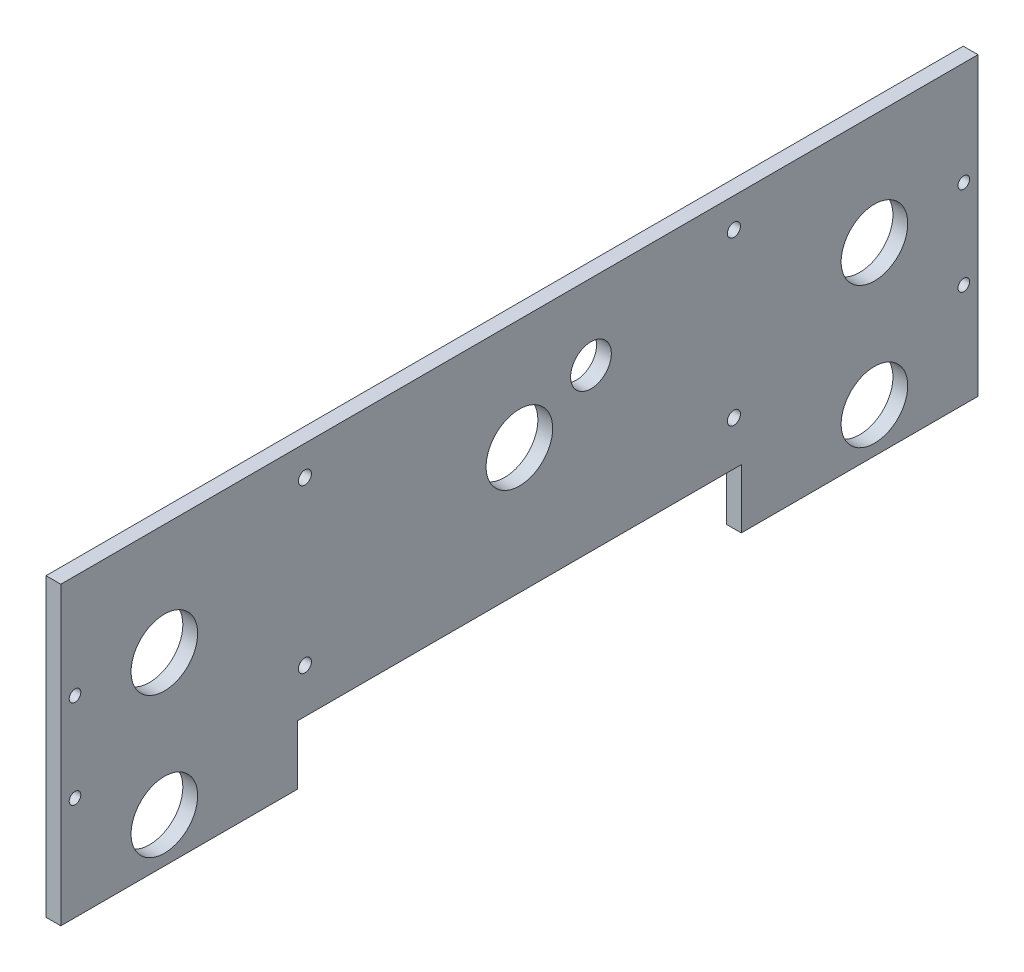
SolidWorks part; units mm, degrees
material "6061-T6 (SS)"
ref_plane "Front Plane" through (0, 0, 0) normal (0, 0, 1) x (1, 0, 0)
ref_plane "Top Plane" through (0, 0, 0) normal (0, 1, 0) x (1, 0, 0)
ref_plane "Right Plane" through (0, 0, 0) normal (1, 0, 0) x (0, 0, -1)
sketch "Sketch1" plane through (0, 0, 0) normal (1, 0, 0) x (0, 0, -1)
  line L1 (-196.85, 63.5) -> (196.85, 63.5)
  line L2 (-196.85, 63.5) -> (-196.85, -63.5)
  line L3 (-196.85, -63.5) -> (196.85, -63.5)
  line L4 (196.85, 63.5) -> (196.85, -63.5)
  line L5 (-196.85, 63.5) -> (196.85, -63.5) construction
  line L6 (-196.85, -63.5) -> (196.85, 63.5) construction
  point P0 (0, 0)
  dimension "D1" = 127
  dimension "D2" = 393.7
extrude "Boss-Extrude1" add sketch "Sketch1" along normal blind 6.35
sketch "Sketch2" plane through (6.35, 0, 0) normal (1, 0, 0) x (0, 0, -1)
  line L0 (-196.85, -63.5) -> (196.85, -63.5) construction
  line L1 (-152.4, 15.875) -> (0, 15.875) construction
  line L2 (-76.2, -34.925) -> (-76.2, 15.875) construction
  line L3 (0, 15.875) -> (152.4, 15.875) construction
  line L4 (76.2, -34.925) -> (76.2, 15.875) construction
  line L5 (196.85, 63.5) -> (-196.85, 63.5) construction
  line L6 (65.278, 53.34) -> (-56.642, 53.34) construction
  line L7 (65.278, 53.34) -> (65.278, -13.97) construction
  line L8 (65.278, -13.97) -> (-56.642, -13.97) construction
  line L9 (-56.642, 53.34) -> (-56.642, -13.97) construction
  line L10 (-196.85, -63.5) -> (196.85, -63.5) construction
  circle A0 centre (0, 15.875) radius 14.2875
  circle A1 centre (-152.4, 15.875) radius 14.2875
  circle A2 centre (152.4, 15.875) radius 14.2875
  circle A3 centre (-152.4, 15.875) radius 38.1 construction
  circle A4 centre (0, 15.875) radius 38.1 construction
  circle A5 centre (152.4, 15.875) radius 38.1 construction
  circle A6 centre (-76.2, -34.925) radius 6.35 construction
  circle A7 centre (76.2, -34.925) radius 6.35 construction
  circle A8 centre (-76.2, 9.525) radius 6.35 construction
  circle A9 centre (76.2, 9.525) radius 6.35 construction
  circle A11 centre (-152.4, -44.45) radius 14.2875
  circle A12 centre (152.4, -44.45) radius 14.2875
  circle A13 centre (0, 15.875) radius 29.21 construction
  circle A14 centre (30.7172, 31.115) radius 5.08 construction
  circle A15 centre (30.7172, 31.115) radius 8.75
  point P11 (0, 0)
  dimension "D1" = 28.575
  dimension "D5" = 76.2
  dimension "D7" = 12.7
  dimension "D14" = 28.575
  dimension "D15" = 19.05
  dimension "D17" = 28.575
  dimension "D20" = 58.42
  dimension "D21" = 10.16
  dimension "D22" = 17.5001
  dimension "D2" = 79.375
  dimension "D3" = 152.4
  dimension "D4" = 152.4
  dimension "D6" = 0
  dimension "D8" = 28.575
  dimension "D9" = 44.45
  dimension "D10" = 56.642
  dimension "D11" = 121.92
  dimension "D12" = 10.16
  dimension "D13" = 49.53
  dimension "D16" = 152.4
  dimension "D18" = 19.05
  dimension "D19" = 152.4
  dimension "D23" = 15.24
extrude "Cut-Extrude1" cut sketch "Sketch2" against normal through all
sketch "Sketch3" plane through (6.35, 0, 0) normal (1, 0, 0) x (0, 0, -1)
  line L0 (-190.754, 19.05) -> (-190.754, -19.05) construction
  line L1 (-196.85, 63.5) -> (-196.85, -63.5) construction
  point P2 (-190.754, 0)
  point P3 (-196.85, 0)
  dimension "D1" = 38.1
  dimension "D2" = 6.096
hole_wizard "#10 Clearance Hole1" positions "Sketch4" profile "Sketch6" hole size "#10" standard "ANSI Inch" end condition through all
sketch "Sketch4" plane through (6.35, 0, 0) normal (1, 0, 0) x (0, 0, -1)
  line L3 (196.85, -63.5) -> (196.85, 63.5) construction
  point P0 (-190.754, 19.05)
  point P3 (-190.754, -19.05)
  point P8 (190.754, 19.05)
  point P10 (190.754, -19.05)
  dimension "D1" = 6.096
  dimension "D2" = 6.096
sketch "Sketch6" plane through (6.35, 19.05, 190.754) normal (0, 1, 0) x (0, 0, -1)
  line L0 (0, 0) -> (0, 6.35)
  line L1 (0, 6.35) -> (2.4892, 6.35)
  line L2 (2.4892, 6.35) -> (2.4892, 0)
  line L5 (2.4892, 0) -> (0, 0)
  line L11 (0, -6.35) -> (0, 107.95) construction
  dimension "Thru Hole Dia." = 4.9784
  dimension "Thru Hole Depth" = 6.35
sketch "Sketch23" plane through (6.35, 0, 0) normal (1, 0, 0) x (0, 0, -1)
  line L0 (-95.25, -63.5) -> (-95.25, -38.1)
  line L1 (-196.85, -63.5) -> (196.85, -63.5) construction
  line L2 (-95.25, -38.1) -> (95.25, -38.1)
  line L3 (95.25, -38.1) -> (95.25, -63.5)
  line L4 (-196.85, 63.5) -> (-196.85, -63.5) construction
  line L5 (196.85, -63.5) -> (196.85, 63.5) construction
  line L6 (-95.25, -63.5) -> (95.25, -63.5)
  dimension "D1" = 25.4
  dimension "D2" = 101.6
  dimension "D3" = 101.6
extrude "Cut-Extrude6" cut sketch "Sketch23" against normal through all
sketch "Sketch24" plane through (0, 0, 0) normal (-1, 0, 0) x (0, 0, 1)
  line L0 (-196.85, -63.5) -> (-196.85, 63.5) construction
  line L1 (-196.85, 63.5) -> (196.85, 63.5) construction
  point P0 (-92.075, -19.05)
  point P1 (-92.075, 50.8)
  point P2 (92.075, -19.05)
  point P4 (92.075, 50.8)
  point P10 (0, 0)
  point P11 (0, 0)
  point P12 (0, 0)
  point P13 (0, 0)
  point P14 (0, 0)
  dimension "D1" = 69.85
  dimension "D2" = 104.775
  dimension "D3" = 12.7
  dimension "D4" = 12.7
  dimension "D5" = 69.85
  dimension "D6" = 184.15
hole_wizard "CSK for #10 Flat Head Machine Screw2" positions "Sketch25" profile "Sketch26" countersink size "#10" standard "ANSI Inch" end condition through all
sketch "Sketch25" plane through (0, 0, 0) normal (-1, 0, 0) x (0, 0, 1)
  point P0 (-92.075, 50.8)
  point P3 (-92.075, -19.05)
  point P6 (92.075, -19.05)
  point P9 (92.075, 50.8)
sketch "Sketch26" plane through (0, 50.8, -92.075) normal (0, 1, 0) x (0, 0, 1)
  line L0 (0, 0) -> (0, 6.35)
  line L1 (0, 6.35) -> (2.8067, 6.35)
  line L2 (2.8067, 6.35) -> (2.8067, 2.396)
  line L3 (2.8067, 2.396) -> (4.8895, 0)
  line L5 (4.8895, 0) -> (0, 0)
  line L6 (-2.8067, 2.396) -> (-4.8895, 0) construction
  line L11 (0, -6.35) -> (0, 107.95) construction
  dimension "Thru Hole Dia." = 5.6134
  dimension "Thru Hole Depth" = 6.35
  dimension "Near C'Sink Dia." = 9.779
  dimension "Near C'Sink Angle" = 82
